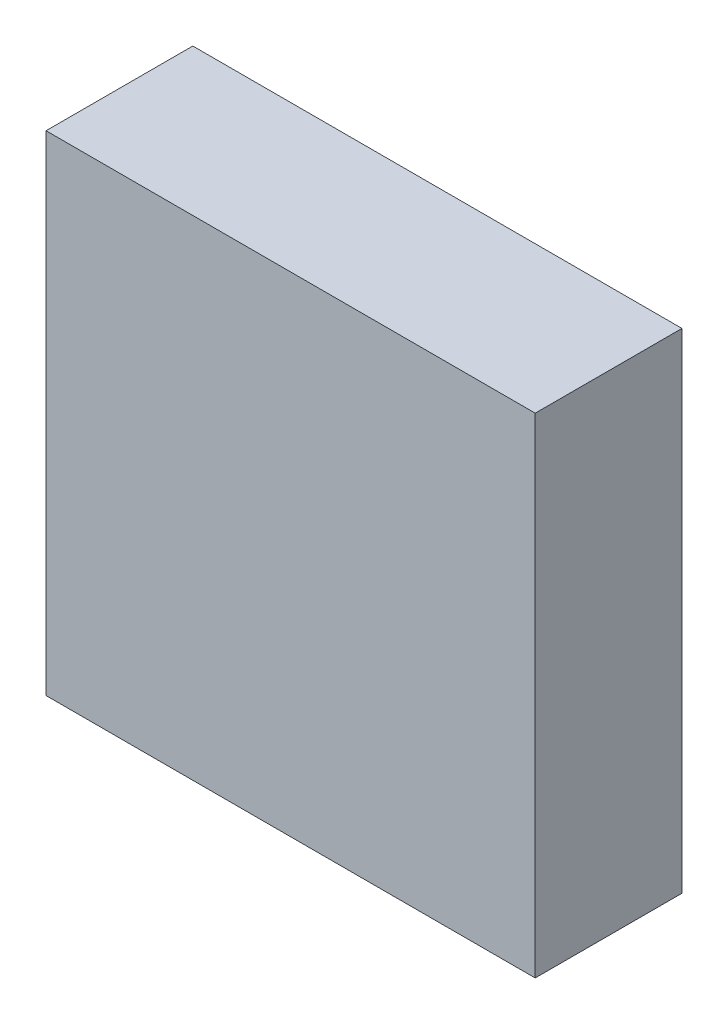
SolidWorks part; units mm, degrees
material "Silicon Dioxide"
ref_plane "Front Plane" through (0, 0, 0) normal (0, 0, 1) x (1, 0, 0)
ref_plane "Top Plane" through (0, 0, 0) normal (0, 1, 0) x (1, 0, 0)
ref_plane "Right Plane" through (0, 0, 0) normal (1, 0, 0) x (0, 0, -1)
sketch "Sketch1" plane through (0, 0, 0) normal (0, 0, 1) x (1, 0, 0)
  line L1 (-75.6362, 48.0134) -> (24.3638, 48.0134)
  line L2 (-75.6362, 48.0134) -> (-75.6362, -51.9866)
  line L3 (-75.6362, -51.9866) -> (24.3638, -51.9866)
  line L4 (24.3638, 48.0134) -> (24.3638, -51.9866)
  dimension "D1" = 100
  dimension "D2" = 100
extrude "Boss-Extrude1" add sketch "Sketch1" along normal blind 30
